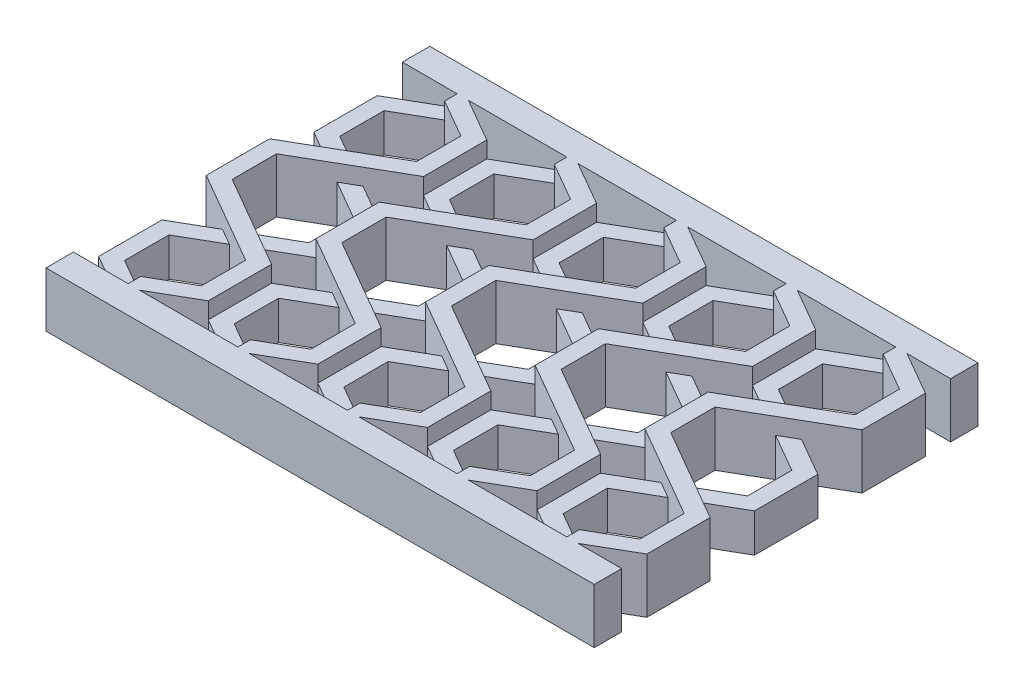
SolidWorks part; units mm, degrees
ref_plane "Front Plane" through (0, 0, 0) normal (0, 0, 1) x (1, 0, 0)
ref_plane "Top Plane" through (0, 0, 0) normal (0, 1, 0) x (1, 0, 0)
ref_plane "Right Plane" through (0, 0, 0) normal (1, 0, 0) x (0, 0, -1)
sketch "Sketch1" plane through (0, 0, 0) normal (0, 1, 0) x (1, 0, 0)
  line L0 (-50, 30) -> (50, 30)
  line L1 (-50, -35) -> (50, -35)
  line L2 (-50, -35) -> (-50, 35)
  line L3 (-50, 35) -> (50, 35)
  line L4 (50, -35) -> (50, 35)
  line L5 (-50, -35) -> (50, 35) construction
  line L6 (-50, 35) -> (50, -35) construction
  line L8 (-50, -30) -> (50, -30)
  line L10 (-45, -30) -> (-45, 30) construction
  line L11 (45, -30) -> (45, 30) construction
  line L12 (-45, 30) -> (45, 30) construction
  line L13 (-45, -30) -> (45, -30) construction
  line L14 (0, 8.0829) -> (-7, 4.0415)
  line L15 (0, 11.547) -> (-10, 5.7735)
  line L16 (-10, 5.7735) -> (-10, -5.7735)
  line L17 (-10, -5.7735) -> (0, -11.547)
  line L18 (0, -11.547) -> (10, -5.7735)
  line L19 (10, -5.7735) -> (10, 5.7735)
  line L20 (10, 5.7735) -> (0, 11.547)
  line L21 (-7, 4.0415) -> (-7, -4.0415)
  line L22 (-7, -4.0415) -> (0, -8.0829)
  line L23 (0, -8.0829) -> (7, -4.0415)
  line L24 (7, -4.0415) -> (7, 4.0415)
  line L25 (7, 4.0415) -> (0, 8.0829)
  line L26 (20, 8.0829) -> (13, 4.0415)
  line L27 (13, 4.0415) -> (13, -4.0415)
  line L28 (13, -4.0415) -> (20, -8.0829)
  line L29 (20, -8.0829) -> (27, -4.0415)
  line L30 (27, -4.0415) -> (27, 4.0415)
  line L31 (27, 4.0415) -> (20, 8.0829)
  line L32 (20, 11.547) -> (10, 5.7735)
  line L33 (10, 5.7735) -> (10, -5.7735)
  line L34 (10, -5.7735) -> (20, -11.547)
  line L35 (20, -11.547) -> (30, -5.7735)
  line L36 (30, -5.7735) -> (30, 5.7735)
  line L37 (30, 5.7735) -> (20, 11.547)
  line L38 (40, 8.0829) -> (33, 4.0415)
  line L39 (33, 4.0415) -> (33, -4.0415)
  line L40 (33, -4.0415) -> (40, -8.0829)
  line L41 (40, -8.0829) -> (47, -4.0415)
  line L42 (47, -4.0415) -> (47, 4.0415)
  line L43 (47, 4.0415) -> (40, 8.0829)
  line L44 (40, 11.547) -> (30, 5.7735)
  line L45 (30, 5.7735) -> (30, -5.7735)
  line L46 (30, -5.7735) -> (40, -11.547)
  line L47 (40, -11.547) -> (50, -5.7735)
  line L48 (50, -5.7735) -> (50, 5.7735)
  line L49 (50, 5.7735) -> (40, 11.547)
  line L62 (-20, 8.0829) -> (-27, 4.0415)
  line L63 (-27, 4.0415) -> (-27, -4.0415)
  line L64 (-27, -4.0415) -> (-20, -8.0829)
  line L65 (-20, -8.0829) -> (-13, -4.0415)
  line L66 (-13, -4.0415) -> (-13, 4.0415)
  line L67 (-13, 4.0415) -> (-20, 8.0829)
  line L68 (-20, 11.547) -> (-30, 5.7735)
  line L69 (-30, 5.7735) -> (-30, -5.7735)
  line L70 (-30, -5.7735) -> (-20, -11.547)
  line L71 (-20, -11.547) -> (-10, -5.7735)
  line L72 (-10, -5.7735) -> (-10, 5.7735)
  line L73 (-10, 5.7735) -> (-20, 11.547)
  line L74 (-40, 8.0829) -> (-47, 4.0415)
  line L75 (-47, 4.0415) -> (-47, -4.0415)
  line L76 (-47, -4.0415) -> (-40, -8.0829)
  line L77 (-40, -8.0829) -> (-33, -4.0415)
  line L78 (-33, -4.0415) -> (-33, 4.0415)
  line L79 (-33, 4.0415) -> (-40, 8.0829)
  line L80 (-40, 11.547) -> (-50, 5.7735)
  line L81 (-50, 5.7735) -> (-50, -5.7735)
  line L82 (-50, -5.7735) -> (-40, -11.547)
  line L83 (-40, -11.547) -> (-30, -5.7735)
  line L84 (-30, -5.7735) -> (-30, 5.7735)
  line L85 (-30, 5.7735) -> (-40, 11.547)
  line L86 (20, 27.7128) -> (13, 23.6714)
  line L87 (13, 23.6714) -> (13, 15.5885)
  line L88 (13, 15.5885) -> (20, 11.547)
  line L89 (20, 11.547) -> (27, 15.5885)
  line L90 (27, 15.5885) -> (27, 23.6714)
  line L91 (27, 23.6714) -> (20, 27.7128)
  line L92 (17.9615, 30) -> (10, 25.4034)
  line L93 (10, 25.4034) -> (10, 13.8564)
  line L94 (10, 13.8564) -> (20, 8.0829)
  line L95 (20, 8.0829) -> (30, 13.8564)
  line L96 (30, 13.8564) -> (30, 25.4034)
  line L97 (30, 25.4034) -> (22.0385, 30)
  line L98 (-2.0385, 30) -> (-10, 25.4034)
  line L99 (-10, 25.4034) -> (-10, 13.8564)
  line L100 (-10, 13.8564) -> (0, 8.0829)
  line L101 (0, 8.0829) -> (10, 13.8564)
  line L102 (10, 13.8564) -> (10, 25.4034)
  line L103 (10, 25.4034) -> (2.0385, 30)
  line L104 (0, 27.7128) -> (-7, 23.6714)
  line L105 (-7, 23.6714) -> (-7, 15.5885)
  line L106 (-7, 15.5885) -> (0, 11.547)
  line L107 (0, 11.547) -> (7, 15.5885)
  line L108 (7, 15.5885) -> (7, 23.6714)
  line L109 (7, 23.6714) -> (0, 27.7128)
  line L110 (-22.0385, 30) -> (-30, 25.4034)
  line L111 (-30, 25.4034) -> (-30, 13.8564)
  line L112 (-30, 13.8564) -> (-20, 8.0829)
  line L113 (-20, 8.0829) -> (-10, 13.8564)
  line L114 (-10, 13.8564) -> (-10, 25.4034)
  line L115 (-10, 25.4034) -> (-17.9615, 30)
  line L116 (-20, 27.7128) -> (-27, 23.6714)
  line L117 (-27, 23.6714) -> (-27, 15.5885)
  line L118 (-27, 15.5885) -> (-20, 11.547)
  line L119 (-20, 11.547) -> (-13, 15.5885)
  line L120 (-13, 15.5885) -> (-13, 23.6714)
  line L121 (-13, 23.6714) -> (-20, 27.7128)
  line L122 (-42.0385, 30) -> (-50, 25.4034)
  line L123 (-50, 25.4034) -> (-50, 13.8564)
  line L124 (-50, 13.8564) -> (-40, 8.0829)
  line L125 (-40, 8.0829) -> (-30, 13.8564)
  line L126 (-30, 13.8564) -> (-30, 25.4034)
  line L127 (-30, 25.4034) -> (-37.9615, 30)
  line L128 (-40, 27.7128) -> (-47, 23.6714)
  line L129 (-47, 23.6714) -> (-47, 15.5885)
  line L130 (-47, 15.5885) -> (-40, 11.547)
  line L131 (-40, 11.547) -> (-33, 15.5885)
  line L132 (-33, 15.5885) -> (-33, 23.6714)
  line L133 (-33, 23.6714) -> (-40, 27.7128)
  line L134 (37.9615, 30) -> (30, 25.4034)
  line L135 (30, 25.4034) -> (30, 13.8564)
  line L136 (30, 13.8564) -> (40, 8.0829)
  line L137 (40, 8.0829) -> (50, 13.8564)
  line L138 (50, 13.8564) -> (50, 25.4034)
  line L139 (50, 25.4034) -> (42.0385, 30)
  line L140 (40, 27.7128) -> (33, 23.6714)
  line L141 (33, 23.6714) -> (33, 15.5885)
  line L142 (33, 15.5885) -> (40, 11.547)
  line L143 (40, 11.547) -> (47, 15.5885)
  line L144 (47, 15.5885) -> (47, 23.6714)
  line L145 (47, 23.6714) -> (40, 27.7128)
  line L146 (-40, -11.547) -> (-47, -15.5885)
  line L147 (-47, -15.5885) -> (-47, -23.6714)
  line L148 (-47, -23.6714) -> (-40, -27.7128)
  line L149 (-40, -27.7128) -> (-33, -23.6714)
  line L150 (-33, -23.6714) -> (-33, -15.5885)
  line L151 (-33, -15.5885) -> (-40, -11.547)
  line L152 (-40, -8.0829) -> (-50, -13.8564)
  line L153 (-50, -13.8564) -> (-50, -25.4034)
  line L154 (-50, -25.4034) -> (-42.0385, -30)
  line L155 (-37.9615, -30) -> (-30, -25.4034)
  line L156 (-30, -25.4034) -> (-30, -13.8564)
  line L157 (-30, -13.8564) -> (-40, -8.0829)
  line L158 (-20, -11.547) -> (-27, -15.5885)
  line L159 (-27, -15.5885) -> (-27, -23.6714)
  line L160 (-27, -23.6714) -> (-20, -27.7128)
  line L161 (-20, -27.7128) -> (-13, -23.6714)
  line L162 (-13, -23.6714) -> (-13, -15.5885)
  line L163 (-13, -15.5885) -> (-20, -11.547)
  line L164 (-20, -8.0829) -> (-30, -13.8564)
  line L165 (-30, -13.8564) -> (-30, -25.4034)
  line L166 (-30, -25.4034) -> (-22.0385, -30)
  line L167 (-17.9615, -30) -> (-10, -25.4034)
  line L168 (-10, -25.4034) -> (-10, -13.8564)
  line L169 (-10, -13.8564) -> (-20, -8.0829)
  line L170 (0, -11.547) -> (-7, -15.5885)
  line L171 (-7, -15.5885) -> (-7, -23.6714)
  line L172 (-7, -23.6714) -> (0, -27.7128)
  line L173 (0, -27.7128) -> (7, -23.6714)
  line L174 (7, -23.6714) -> (7, -15.5885)
  line L175 (7, -15.5885) -> (0, -11.547)
  line L176 (0, -8.0829) -> (-10, -13.8564)
  line L177 (-10, -13.8564) -> (-10, -25.4034)
  line L178 (-10, -25.4034) -> (-2.0385, -30)
  line L179 (2.0385, -30) -> (10, -25.4034)
  line L180 (10, -25.4034) -> (10, -13.8564)
  line L181 (10, -13.8564) -> (0, -8.0829)
  line L182 (20, -11.547) -> (13, -15.5885)
  line L183 (13, -15.5885) -> (13, -23.6714)
  line L184 (13, -23.6714) -> (20, -27.7128)
  line L185 (20, -27.7128) -> (27, -23.6714)
  line L186 (27, -23.6714) -> (27, -15.5885)
  line L187 (27, -15.5885) -> (20, -11.547)
  line L188 (20, -8.0829) -> (10, -13.8564)
  line L189 (10, -13.8564) -> (10, -25.4034)
  line L190 (10, -25.4034) -> (17.9615, -30)
  line L191 (22.0385, -30) -> (30, -25.4034)
  line L192 (30, -25.4034) -> (30, -13.8564)
  line L193 (30, -13.8564) -> (20, -8.0829)
  line L194 (40, -11.547) -> (33, -15.5885)
  line L195 (33, -15.5885) -> (33, -23.6714)
  line L196 (33, -23.6714) -> (40, -27.7128)
  line L197 (40, -27.7128) -> (47, -23.6714)
  line L198 (47, -23.6714) -> (47, -15.5885)
  line L199 (47, -15.5885) -> (40, -11.547)
  line L200 (40, -8.0829) -> (30, -13.8564)
  line L201 (30, -13.8564) -> (30, -25.4034)
  line L202 (30, -25.4034) -> (37.9615, -30)
  line L203 (42.0385, -30) -> (50, -25.4034)
  line L204 (50, -25.4034) -> (50, -13.8564)
  line L205 (50, -13.8564) -> (40, -8.0829)
  line L206 (-40, 30) -> (-40, 11.547)
  line L207 (-20, 30) -> (-20, 11.547)
  line L208 (0, 30) -> (0, 11.547)
  line L209 (20, 30) -> (20, 11.547)
  line L210 (40, 30) -> (40, 11.547)
  line L211 (40, -11.547) -> (40, -30)
  line L212 (20, -11.547) -> (20, -30)
  line L213 (0, -11.547) -> (0, -30)
  line L214 (0, 8.0829) -> (0, -8.0829)
  line L215 (-20, 8.0829) -> (-20, -8.0829)
  line L216 (-40, 8.0829) -> (-40, -8.0829)
  line L217 (-40, -11.547) -> (-40, -30)
  line L218 (-20, -11.547) -> (-20, -30)
  line L219 (40, 8.0829) -> (40, -8.0829)
  line L220 (20, 8.0829) -> (20, -8.0829)
  circle A0 centre (0, 0) radius 10 construction
  point P0 (0, 0)
  dimension "D1" = 70
  dimension "D2" = 100
  dimension "D5" = 10
  dimension "D6" = 3
  dimension "D7" = 3
  dimension "D4" = 3
  dimension "D3" = 5
  dimension "D8" = 2
  dimension "D9" = 2
extrude "Boss-Extrude4" add sketch "Sketch1" along normal blind 10 contours L0 L206 L133 L132 L131 L85 L125 L111 L127 | L124 L125 L85 L80 | L152 L76 L75 L74 L124 L80 L2 L82 | L83 L157 L152 L82 | L149 L217 L8 L155 L156 L157 L83 L151 L150 | L8 L2 L1 L4 | L0 L4 L3 L2 | L0 L207 L121 L120 L119 L73 L113 L99 L115 | L112 L113 L73 L68 | L164 L64 L63 L62 L112 L68 L69 L70 | L71 L169 L164 L70 | L161 L218 L8 L167 L168 L169 L71 L163 L162 | L0 L208 L109 L108 L107 L20 L101 L93 L103 | L100 L101 L20 L15 | L176 L22 L21 L14 L100 L15 L16 L17 | L18 L181 L176 L17 | L173 L213 L8 L179 L180 L181 L18 L175 L174 | L0 L209 L91 L90 L89 L37 L95 L96 L97 | L94 L95 L37 L32 | L188 L28 L27 L26 L94 L32 L19 L34 | L35 L193 L188 L34 | L185 L212 L8 L191 L192 L193 L35 L187 L186 | L0 L210 L145 L144 L143 L49 L137 L4 L139 | L136 L137 L49 L44 | L200 L40 L39 L38 L136 L44 L36 L46 | L47 L205 L200 L46 | L197 L211 L8 L203 L4 L205 L47 L199 L198 region at (0, 0, -32.5) region at (-38.9808, 0, -29.7747) region at (-46.3898, 0, -7.6034) region at (-40, 0, -9.815) region at (45.9066, 0, -27.5066) region at (-18.9808, 0, -29.7747) region at (-40, 0, 9.815) region at (-21.6102, 0, -8.7581) region at (-20, 0, -9.815) region at (-38.3874, 0, 10.8761) region at (40, 0, -9.815) region at (0, 0, 32.5) region at (25.9066, 0, -27.5066) region at (36.3898, 0, -6.253) region at (1.0192, 0, -29.7747) region at (-20, 0, 9.815) region at (49.7747, 0, 19.6299) region at (40, 0, 9.815) region at (-1.6102, 0, -8.7581) region at (0, 0, -9.815) region at (-13.6126, 0, 12.0308) region at (20, 0, -9.815) region at (16.3898, 0, -6.253) region at (29.7747, 0, 19.6299) region at (0, 0, 9.815) region at (20, 0, 9.815) region at (6.3874, 0, 12.0308)
extrude "Boss-Extrude5" add sketch "Sketch1<7>" along normal blind 7 contours L206 L0 L122 L2 L124 L80 L130 L129 L128 | L217 L148 L147 L146 L82 L152 L2 L154 L8 | L157 L83 L69 L85 L125 L79 L78 L77 | L207 L0 L110 L111 L112 L68 L118 L117 L116 | L169 L71 L16 L73 L113 L67 L66 L65 | L218 L160 L159 L158 L70 L164 L156 L166 L8 | L208 L0 L98 L99 L100 L15 L106 L105 L104 | L181 L18 L19 L20 L101 L25 L24 L23 | L213 L172 L171 L170 L17 L176 L168 L178 L8 | L209 L0 L92 L93 L94 L32 L88 L87 L86 | L193 L35 L36 L37 L95 L31 L30 L29 | L212 L184 L183 L182 L34 L188 L180 L190 L8 | L211 L196 L195 L194 L46 L200 L192 L202 L8 | L205 L47 L4 L49 L137 L43 L42 L41 | L210 L0 L134 L96 L136 L44 L142 L141 L140 region at (-41.0192, 0, -29.7747) region at (-21.0192, 0, -29.7747) region at (-38.3898, 0, -8.7581) region at (-46.3874, 0, 12.0308) region at (39.7747, 0, -28.8564) region at (49.7797, 0, 0) region at (-1.0192, 0, -29.7747) region at (-18.3898, 0, -8.7581) region at (-26.3874, 0, 12.0308) region at (19.7747, 0, -28.8564) region at (26.3898, 0, -7.6034) region at (36.3874, 0, 13.3726) region at (1.6102, 0, -8.7581) region at (-6.3874, 0, 12.0308) region at (18.3874, 0, 10.8761)
sketch "Sketch1<7>" plane through (0, 0, 0) normal (0, 1, 0) x (1, 0, 0) same geometry as "Sketch1"
